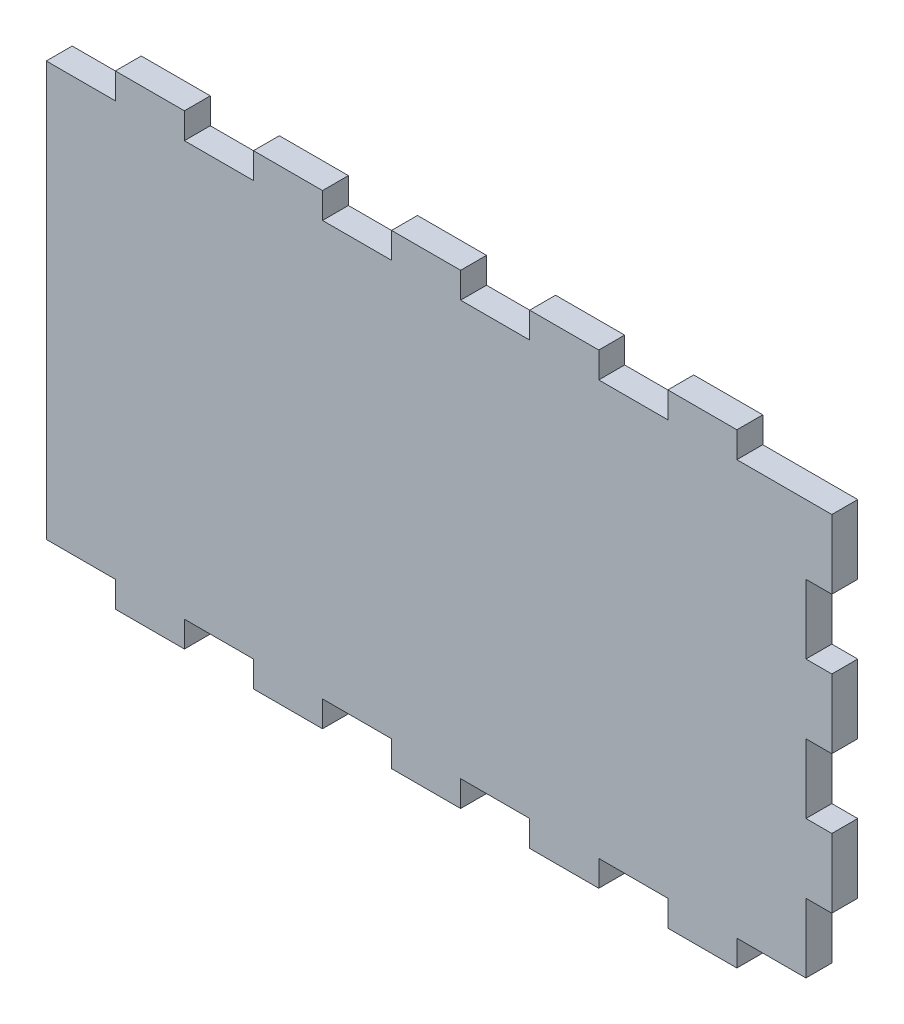
SolidWorks part; units mm, degrees
ref_plane "Front Plane" through (0, 0, 0) normal (0, 0, 1) x (1, 0, 0)
ref_plane "Top Plane" through (0, 0, 0) normal (0, 1, 0) x (1, 0, 0)
ref_plane "Right Plane" through (0, 0, 0) normal (1, 0, 0) x (0, 0, -1)
sketch "Sketch1" plane through (0, 0, 0) normal (0, 0, 1) x (1, 0, 0)
  line L1 (-139.7, -76.2) -> (139.7, -76.2)
  line L2 (-139.7, -76.2) -> (-139.7, 76.2)
  line L3 (-139.7, 76.2) -> (139.7, 76.2)
  line L4 (139.7, -76.2) -> (139.7, 76.2)
  line L5 (-139.7, -76.2) -> (139.7, 76.2) construction
  line L6 (-139.7, 76.2) -> (139.7, -76.2) construction
  point P0 (0, 0)
  dimension "D1" = 279.4
  dimension "D2" = 152.4
extrude "Boss-Extrude1" add sketch "Sketch1" along normal blind 9.525
sketch "Sketch2" plane through (0, -76.2, 0) normal (0, -1, 0) x (1, 0, 0)
  line L0 (-139.7, 0) -> (139.7, 0) construction
  line L1 (-114.3, 0) -> (-88.9, 0)
  line L2 (-114.3, 0) -> (-114.3, 9.525)
  line L3 (-114.3, 9.525) -> (-88.9, 9.525)
  line L4 (-88.9, 0) -> (-88.9, 9.525)
  line L5 (-139.7, 9.525) -> (139.7, 9.525) construction
  line L6 (-139.7, 9.525) -> (-139.7, 0) construction
  point P10 (-139.7, 4.7625)
  dimension "D1" = 25.4
  dimension "D2" = 25.4
extrude "Boss-Extrude2" add sketch "Sketch2" along normal blind 9.525
pattern_linear "LPattern1" count 5 spacing 50.8 along (1, 0, 0) of "Boss-Extrude2"
mirror "Mirror1" about plane through (0, 0, 0) normal (0, 1, 0) of "LPattern1"
sketch "Sketch3" plane through (139.7, 0, 0) normal (1, 0, 0) x (0, 0, -1)
  line L0 (0, 94.2975) -> (0, -94.2975) construction
  line L1 (-9.525, 76.2) -> (0, 76.2)
  line L2 (-9.525, 76.2) -> (-9.525, 50.8)
  line L3 (-9.525, 50.8) -> (0, 50.8)
  line L4 (0, 76.2) -> (0, 50.8)
  dimension "D1" = 25.4
extrude "Boss-Extrude3" add sketch "Sketch3" along normal blind 9.525
pattern_linear "LPattern2" count 3 spacing 50.8 along (0, -1, 0) of "Boss-Extrude3"
